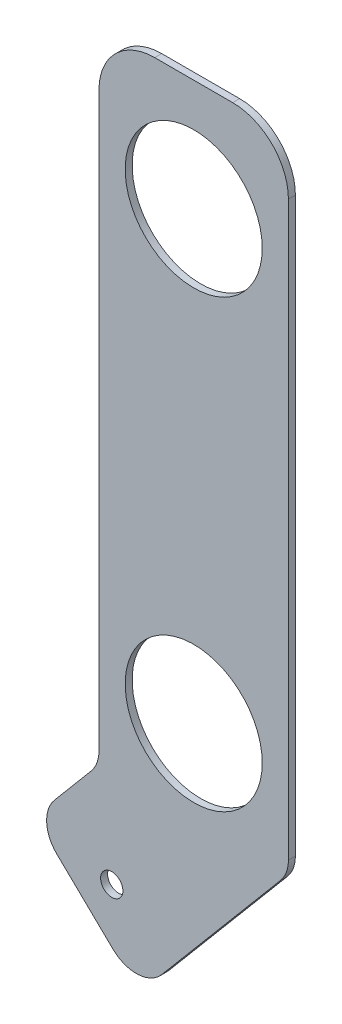
SolidWorks part; units mm, degrees
material "6061 Alloy"
ref_plane "Front Plane" through (0, 0, 0) normal (0, 0, 1) x (1, 0, 0)
ref_plane "Top Plane" through (0, 0, 0) normal (0, 1, 0) x (1, 0, 0)
ref_plane "Right Plane" through (0, 0, 0) normal (1, 0, 0) x (0, 0, -1)
sketch "Sketch1" plane through (0, 0, 0) normal (0, 0, 1) x (1, 0, 0)
  line L0 (0, 0) -> (0, -101.6) construction
  line L1 (21.59, -120.5575) -> (-21.59, -120.5575) construction
  line L2 (-8.89, 25.4) -> (8.89, 25.4)
  line L3 (-21.59, 12.7) -> (-21.59, -117.7751)
  line L5 (21.59, 12.7) -> (21.59, -117.7751)
  line L9 (-23.3829, -122.6853) -> (-31.7351, -132.597)
  line L10 (-36.322, 25.4) -> (20.828, 25.4) construction
  line L11 (-36.322, 25.4) -> (-36.322, -203.2) construction
  line L12 (-36.322, -203.2) -> (20.828, -203.2) construction
  line L13 (20.828, 25.4) -> (20.828, -203.2) construction
  line L14 (-31.203, -142.9869) -> (-18.3873, -155.3705)
  line L15 (-7.2652, -154.801) -> (19.7971, -122.6853)
  circle A0 centre (0, 0) radius 38.1 construction
  circle A1 centre (0, -101.6) radius 38.1 construction
  circle A2 centre (0, 0) radius 15.621
  circle A3 centre (0, -101.6) radius 15.621
  arc A6 (8.89, 25.4) -> (21.59, 12.7) centre (8.89, 12.7) cw
  arc A7 (-8.89, 25.4) -> (-21.59, 12.7) centre (-8.89, 12.7) ccw
  circle A10 centre (-18.6799, -142.7255) radius 2.54
  arc A11 (-31.7351, -132.597) -> (-31.203, -142.9869) centre (-25.908, -137.5071) ccw
  arc A12 (-18.3873, -155.3705) -> (-7.2652, -154.801) centre (-13.0923, -149.8908) ccw
  arc A13 (-23.3829, -122.6853) -> (-21.59, -117.7751) centre (-29.21, -117.7751) ccw
  arc A14 (19.7971, -122.6853) -> (21.59, -117.7751) centre (13.97, -117.7751) ccw
  point P13 (-192.705, 39.2708)
  point P20 (21.59, 25.4)
  point P23 (-21.59, 25.4)
  point P29 (-18.7273, -143.3951)
  point P30 (-16.8862, -145.5042)
  point P31 (-36.322, -138.0404)
  dimension "D2" = 76.2
  dimension "D3" = 76.2
  dimension "D4" = 31.242
  dimension "D5" = 31.242
  dimension "D10" = 228.6
  dimension "D11" = 36.322
  dimension "D13" = 5.08
  dimension "D19" = 7.62
  dimension "D20" = 7.62
  dimension "D21" = 12.7
  dimension "D1" = 101.6
  dimension "D6" = 43.18
  dimension "D7" = 21.59
  dimension "D8" = 25.4
  dimension "D9" = 57.15
  dimension "D12" = 25.4
  dimension "D14" = 33.02
  dimension "D15" = 16.51
  dimension "D16" = 8.89
  dimension "D17" = 44.018
  dimension "D18" = 18.9575
extrude "Boss-Extrude1" add sketch "Sketch1" along normal blind 1.5875
